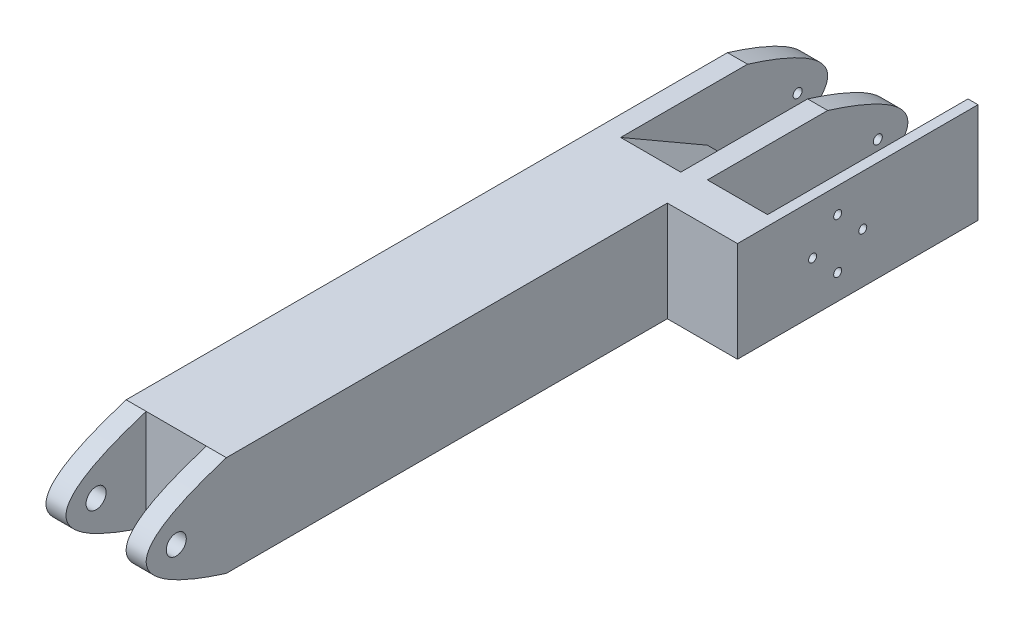
SolidWorks part; units mm, degrees
ref_plane "Front Plane" through (0, 0, 0) normal (0, 0, 1) x (1, 0, 0)
ref_plane "Top Plane" through (0, 0, 0) normal (0, 1, 0) x (1, 0, 0)
ref_plane "Right Plane" through (0, 0, 0) normal (1, 0, 0) x (0, 0, -1)
sketch "Sketch1" plane through (0, 0, 0) normal (1, 0, 0) x (0, 0, -1)
  line L0 (-255.8715, 42.046) -> (44.1285, 42.046)
  line L3 (-255.8715, -7.954) -> (44.1285, -7.954)
  circle A0 centre (-280.8715, 17.046) radius 5
  circle A1 centre (69.1285, 17.046) radius 2.25
  spline S0 degree 2 poles (44.1285, 42.046) (124.1285, 17.046) (44.1285, -7.954) knots 0 0 0 1 1 1
  spline S1 degree 2 poles (-255.8715, 42.046) (-335.8715, 17.046) (-255.8715, -7.954) knots 0 0 0 1 1 1
  dimension "D6" = 40
  dimension "D8" = 10
  dimension "D9" = 15
  dimension "D10" = 4.5
  dimension "D1" = 300
  dimension "D2" = 50
  dimension "D3" = 25
  dimension "D4" = 40
  dimension "D5" = 15
  dimension "D7" = 0
extrude "Boss-Extrude1" add sketch "Sketch1" along normal blind 50
sketch "Sketch2" plane through (0, 0, 0) normal (0, 1, 0) x (1, 0, 0)
  line L0 (50, 84.1285) -> (0, 84.1285) construction
  line L1 (10, 84.1285) -> (40, 84.1285)
  line L2 (10, 84.1285) -> (10, 24.1285)
  line L3 (10, 24.1285) -> (40, 24.1285)
  line L4 (40, 84.1285) -> (40, 24.1285)
  line L6 (0, 84.1285) -> (0, 44.1285) construction
  dimension "D1" = 10
  dimension "D2" = 10
  dimension "D3" = 60
extrude "Cut-Extrude1" cut sketch "Sketch2" along normal blind 52 and the other way blind 35
sketch "Sketch3" plane through (0, -7.954, 0) normal (0, -1, 0) x (1, 0, 0)
  line L0 (50, 295.8715) -> (0, 295.8715) construction
  line L1 (10, 295.8715) -> (40, 295.8715)
  line L2 (10, 295.8715) -> (10, 255.8715)
  line L3 (10, 255.8715) -> (40, 255.8715)
  line L4 (40, 295.8715) -> (40, 255.8715)
  line L5 (50, 255.8715) -> (0, 255.8715) construction
  dimension "D1" = 10
  dimension "D2" = 10
extrude "Cut-Extrude2" cut sketch "Sketch3" against normal blind 52
sketch "Sketch4" plane through (0, 0, 0) normal (-1, 0, 0) x (0, 0, 1)
  line L1 (-44.1285, 42.046) -> (255.8715, 42.046) construction
  line L5 (-24.1285, 17.046) -> (-24.1285, 42.046)
  line L6 (-24.1285, 42.046) -> (19.1728, 42.046)
  line L7 (-24.1285, 17.046) -> (19.1728, 42.046)
  line L8 (-24.1285, -7.954) -> (-24.1285, 42.046) construction
  dimension "D1" = 25
  dimension "D2" = 60
  dimension "D3" = 0
extrude "Cut-Extrude3" cut sketch "Sketch4" against normal blind 30 from offset 10 offset against normal yes
sketch "Sketch5" plane through (0, 0, 0) normal (-1, 0, 0) x (0, 0, 1)
  line L0 (-24.1285, -7.954) -> (-24.1285, 17.046)
  line L1 (-24.1285, 17.046) -> (19.1728, -7.954)
  line L2 (255.8715, -7.954) -> (-44.1285, -7.954) construction
  line L3 (19.1728, -7.954) -> (-24.1285, -7.954)
  line L5 (-24.1285, -7.954) -> (-24.1285, 17.046) construction
  dimension "D1" = 25
  dimension "D2" = 60
  dimension "D3" = 0
extrude "Cut-Extrude4" cut sketch "Sketch5" against normal blind 30 from offset 10 offset against normal yes
sketch "Sketch6" plane through (0, 42.046, 0) normal (0, 1, 0) x (1, 0, 0)
  line L0 (50, -35.8715) -> (85, -35.8715)
  line L1 (50, 44.1285) -> (50, -255.8715) construction
  line L2 (85, -35.8715) -> (85, 84.1285)
  line L3 (85, 84.1285) -> (80, 84.1285)
  line L4 (80, 84.1285) -> (80, -15.8715)
  line L5 (80, -15.8715) -> (50, -15.8715)
  line L9 (50, 84.1285) -> (40, 84.1285) construction
  line L20 (40, 44.1285) -> (40, -19.1728)
  line L21 (40, -19.1728) -> (10, -19.1728)
  line L22 (10, -19.1728) -> (10, 44.1285)
  line L23 (10, 44.1285) -> (0, 44.1285)
  line L24 (0, 44.1285) -> (0, -255.8715)
  line L25 (0, -255.8715) -> (10, -255.8715)
  line L26 (10, -255.8715) -> (40, -255.8715)
  line L27 (40, -255.8715) -> (50, -255.8715)
  line L28 (50, -255.8715) -> (50, 44.1285)
  line L29 (50, 44.1285) -> (40, 44.1285)
  line L38 (50, -35.8715) -> (50, -15.8715)
  dimension "D1" = 30
  dimension "D2" = 5
  dimension "D3" = 100
  dimension "D4" = 20
  dimension "D5" = 0
extrude "Boss-Extrude2" add sketch "Sketch6" against normal blind 50
sketch "Sketch7" plane through (85, 0, 0) normal (1, 0, 0) x (0, 0, -1)
  line L1 (-35.8715, 42.046) -> (84.1285, 42.046) construction
  line L2 (-35.8715, -7.954) -> (-35.8715, 42.046) construction
  circle A0 centre (14.1285, 17.046) radius 15
  dimension "D1" = 30
  dimension "D2" = 25
  dimension "D3" = 50
sketch "Sketch8" plane through (85, 0, 0) normal (1, 0, 0) x (0, 0, -1)
  circle A0 centre (14.1285, 29.546) radius 2
  circle A1 centre (14.1285, 17.046) radius 15 construction
  circle A2 centre (26.6285, 17.046) radius 2
  circle A3 centre (14.1285, 4.546) radius 2
  circle A4 centre (1.6285, 17.046) radius 2
  dimension "D2" = 4
  dimension "D1" = 12.5
  dimension "D3" = 12.5
  dimension "D4" = 12.5
  dimension "D5" = 12.5
extrude "Cut-Extrude5" cut sketch "Sketch8" against normal blind 10
